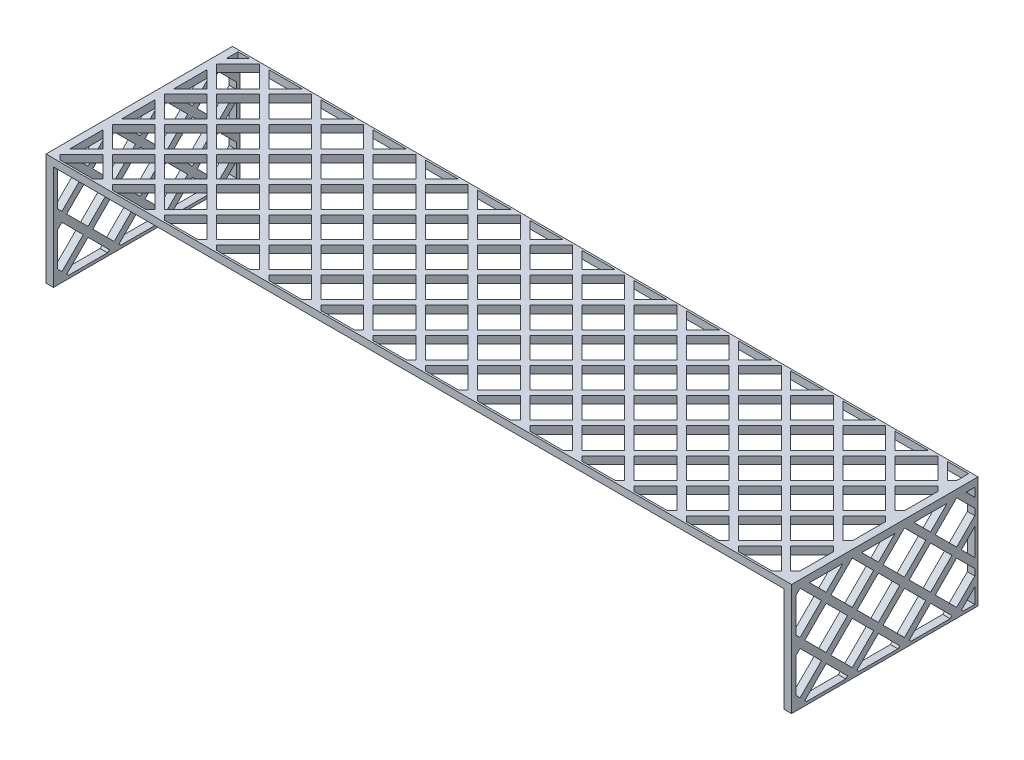
SolidWorks part; units mm, degrees
ref_plane "Front Plane" through (0, 0, 0) normal (0, 0, 1) x (1, 0, 0)
ref_plane "Top Plane" through (0, 0, 0) normal (0, 1, 0) x (1, 0, 0)
ref_plane "Right Plane" through (0, 0, 0) normal (1, 0, 0) x (0, 0, -1)
sketch "Sketch1" plane through (0, 0, 0) normal (0, 1, 0) x (1, 0, 0)
  line L1 (-70.9881, 12.5) -> (29.0119, 12.5)
  line L2 (-70.9881, 12.5) -> (-70.9881, -12.5)
  line L3 (-70.9881, -12.5) -> (29.0119, -12.5)
  line L4 (29.0119, 12.5) -> (29.0119, -12.5)
  point P0 (0, 0)
  dimension "D1" = 25
  dimension "D2" = 100
extrude "Boss-Extrude1" add sketch "Sketch1" along normal blind 1
sketch "Sketch2" plane through (0, 0, 0) normal (0, -1, 0) x (1, 0, 0)
  line L0 (-70.9881, 12.5) -> (29.0119, 12.5) construction
  line L1 (29.0119, -12.5) -> (28.0119, -12.5)
  line L2 (29.0119, -12.5) -> (29.0119, 12.5)
  line L3 (29.0119, 12.5) -> (28.0119, 12.5)
  line L4 (28.0119, -12.5) -> (28.0119, 12.5)
  line L6 (-70.9881, -12.5) -> (-69.9881, -12.5)
  line L7 (-70.9881, -12.5) -> (-70.9881, 12.5)
  line L8 (-70.9881, 12.5) -> (-69.9881, 12.5)
  line L9 (-69.9881, -12.5) -> (-69.9881, 12.5)
extrude "Boss-Extrude2" add sketch "Sketch2" along normal blind 14
sketch "Sketch4" plane through (0, 1, 0) normal (0, 1, 0) x (1, 0, 0)
  line L0 (-67.124, 12.25) -> (-69.9881, 9.3859)
  line L1 (-69.9881, 9.3859) -> (-67.124, 6.5219)
  line L2 (-67.124, 6.5219) -> (-64.2599, 9.3859)
  line L3 (-65.8521, 12.25) -> (-61.3959, 12.25)
  line L5 (-69.3521, -12.25) -> (-64.8959, -12.25)
  line L7 (-64.2599, 9.3859) -> (-67.124, 12.25)
  line L12 (-57.2599, 9.3859) -> (-60.124, 12.25)
  line L13 (-60.124, 12.25) -> (-62.9881, 9.3859)
  line L14 (-62.9881, 9.3859) -> (-60.124, 6.5219)
  line L15 (-60.124, 6.5219) -> (-57.2599, 9.3859)
  line L20 (-60.7599, 5.8859) -> (-63.624, 8.75)
  line L21 (-63.624, 8.75) -> (-66.4881, 5.8859)
  line L22 (-66.4881, 5.8859) -> (-63.624, 3.0219)
  line L23 (-63.624, 3.0219) -> (-60.7599, 5.8859)
  line L24 (-67.7599, 5.8859) -> (-69.9881, 8.1141)
  line L27 (-69.9881, 3.6578) -> (-67.7599, 5.8859)
  line L28 (-70.624, 8.75) -> (-73.4881, 5.8859) [skipped]
  line L29 (-73.4881, 5.8859) -> (-70.624, 3.0219) [skipped]
  line L32 (-65.8521, 12.25) -> (-63.624, 10.0219)
  line L33 (-63.624, 10.0219) -> (-61.3959, 12.25)
  line L34 (-60.7599, 12.8859) -> (-63.624, 15.75) [skipped]
  line L35 (-63.624, 15.75) -> (-66.4881, 12.8859) [skipped]
  line L36 (-64.2599, 2.3859) -> (-67.124, 5.25)
  line L37 (-67.124, 5.25) -> (-69.9881, 2.3859)
  line L38 (-69.9881, 2.3859) -> (-67.124, -0.4781)
  line L39 (-67.124, -0.4781) -> (-64.2599, 2.3859)
  line L40 (-64.2599, -4.6141) -> (-67.124, -1.75)
  line L41 (-67.124, -1.75) -> (-69.9881, -4.6141)
  line L42 (-69.9881, -4.6141) -> (-67.124, -7.4781)
  line L43 (-67.124, -7.4781) -> (-64.2599, -4.6141)
  line L44 (-64.2599, -11.6141) -> (-67.124, -8.75)
  line L45 (-67.124, -8.75) -> (-69.9881, -11.6141)
  line L46 (-69.9881, -11.6141) -> (-69.3521, -12.25)
  line L47 (-64.8959, -12.25) -> (-64.2599, -11.6141)
  line L48 (-69.9881, 8.1141) -> (-69.9881, 3.6578)
  line L50 (-67.7599, -1.1141) -> (-69.9881, 1.1141)
  line L51 (-69.9881, 1.1141) -> (-69.9881, -3.3422)
  line L52 (-69.9881, -3.3422) -> (-67.7599, -1.1141)
  line L53 (-67.7599, -8.1141) -> (-69.9881, -5.8859)
  line L54 (-69.9881, -5.8859) -> (-69.9881, -10.3422)
  line L55 (-69.9881, -10.3422) -> (-67.7599, -8.1141)
  line L56 (-69.9881, 12.25) -> (-69.9881, 10.6578)
  line L57 (-69.9881, 10.6578) -> (-68.3959, 12.25)
  line L58 (-68.3959, 12.25) -> (-69.9881, 12.25)
  line L59 (-57.2599, 9.3859) -> (-60.124, 12.25)
  line L60 (-67.7599, 12.8859) -> (-69.9881, 15.1141) [skipped]
  line L61 (-60.124, 12.25) -> (-62.9881, 9.3859)
  line L62 (-62.9881, 9.3859) -> (-60.124, 6.5219)
  line L63 (-60.124, 6.5219) -> (-57.2599, 9.3859)
  line L64 (-57.2599, 2.3859) -> (-60.124, 5.25)
  line L65 (-60.124, 5.25) -> (-62.9881, 2.3859)
  line L66 (-62.9881, 2.3859) -> (-60.124, -0.4781)
  line L67 (-60.124, -0.4781) -> (-57.2599, 2.3859)
  line L68 (-57.2599, -4.6141) -> (-60.124, -1.75)
  line L69 (-60.124, -1.75) -> (-62.9881, -4.6141)
  line L70 (-62.9881, -4.6141) -> (-60.124, -7.4781)
  line L71 (-60.124, -7.4781) -> (-57.2599, -4.6141)
  line L72 (-62.3521, -12.25) -> (-57.8959, -12.25)
  line L73 (-57.8959, -12.25) -> (-57.2599, -11.6141)
  line L74 (-57.2599, -11.6141) -> (-60.124, -8.75)
  line L75 (-60.124, -8.75) -> (-62.9881, -11.6141)
  line L76 (-62.9881, -11.6141) -> (-62.3521, -12.25)
  line L77 (-50.2599, 9.3859) -> (-53.124, 12.25)
  line L78 (-53.124, 12.25) -> (-55.9881, 9.3859)
  line L79 (-55.9881, 9.3859) -> (-53.124, 6.5219)
  line L80 (-53.124, 6.5219) -> (-50.2599, 9.3859)
  line L81 (-50.2599, 2.3859) -> (-53.124, 5.25)
  line L82 (-53.124, 5.25) -> (-55.9881, 2.3859)
  line L83 (-55.9881, 2.3859) -> (-53.124, -0.4781)
  line L84 (-53.124, -0.4781) -> (-50.2599, 2.3859)
  line L85 (-50.2599, -4.6141) -> (-53.124, -1.75)
  line L86 (-53.124, -1.75) -> (-55.9881, -4.6141)
  line L87 (-55.9881, -4.6141) -> (-53.124, -7.4781)
  line L88 (-53.124, -7.4781) -> (-50.2599, -4.6141)
  line L89 (-55.3521, -12.25) -> (-50.8959, -12.25)
  line L90 (-50.8959, -12.25) -> (-50.2599, -11.6141)
  line L91 (-50.2599, -11.6141) -> (-53.124, -8.75)
  line L92 (-53.124, -8.75) -> (-55.9881, -11.6141)
  line L93 (-55.9881, -11.6141) -> (-55.3521, -12.25)
  line L94 (-43.2599, 9.3859) -> (-46.124, 12.25)
  line L95 (-46.124, 12.25) -> (-48.9881, 9.3859)
  line L96 (-48.9881, 9.3859) -> (-46.124, 6.5219)
  line L97 (-46.124, 6.5219) -> (-43.2599, 9.3859)
  line L98 (-43.2599, 2.3859) -> (-46.124, 5.25)
  line L99 (-46.124, 5.25) -> (-48.9881, 2.3859)
  line L100 (-48.9881, 2.3859) -> (-46.124, -0.4781)
  line L101 (-46.124, -0.4781) -> (-43.2599, 2.3859)
  line L102 (-43.2599, -4.6141) -> (-46.124, -1.75)
  line L103 (-46.124, -1.75) -> (-48.9881, -4.6141)
  line L104 (-48.9881, -4.6141) -> (-46.124, -7.4781)
  line L105 (-46.124, -7.4781) -> (-43.2599, -4.6141)
  line L106 (-48.3521, -12.25) -> (-43.8959, -12.25)
  line L107 (-43.8959, -12.25) -> (-43.2599, -11.6141)
  line L108 (-43.2599, -11.6141) -> (-46.124, -8.75)
  line L109 (-46.124, -8.75) -> (-48.9881, -11.6141)
  line L110 (-48.9881, -11.6141) -> (-48.3521, -12.25)
  line L111 (-36.2599, 9.3859) -> (-39.124, 12.25)
  line L112 (-39.124, 12.25) -> (-41.9881, 9.3859)
  line L113 (-41.9881, 9.3859) -> (-39.124, 6.5219)
  line L114 (-39.124, 6.5219) -> (-36.2599, 9.3859)
  line L115 (-36.2599, 2.3859) -> (-39.124, 5.25)
  line L116 (-39.124, 5.25) -> (-41.9881, 2.3859)
  line L117 (-41.9881, 2.3859) -> (-39.124, -0.4781)
  line L118 (-39.124, -0.4781) -> (-36.2599, 2.3859)
  line L119 (-36.2599, -4.6141) -> (-39.124, -1.75)
  line L120 (-39.124, -1.75) -> (-41.9881, -4.6141)
  line L121 (-41.9881, -4.6141) -> (-39.124, -7.4781)
  line L122 (-39.124, -7.4781) -> (-36.2599, -4.6141)
  line L123 (-41.3521, -12.25) -> (-36.8959, -12.25)
  line L124 (-36.8959, -12.25) -> (-36.2599, -11.6141)
  line L125 (-36.2599, -11.6141) -> (-39.124, -8.75)
  line L126 (-39.124, -8.75) -> (-41.9881, -11.6141)
  line L127 (-41.9881, -11.6141) -> (-41.3521, -12.25)
  line L128 (-29.2599, 9.3859) -> (-32.124, 12.25)
  line L129 (-32.124, 12.25) -> (-34.9881, 9.3859)
  line L130 (-34.9881, 9.3859) -> (-32.124, 6.5219)
  line L131 (-32.124, 6.5219) -> (-29.2599, 9.3859)
  line L132 (-29.2599, 2.3859) -> (-32.124, 5.25)
  line L133 (-32.124, 5.25) -> (-34.9881, 2.3859)
  line L134 (-34.9881, 2.3859) -> (-32.124, -0.4781)
  line L135 (-32.124, -0.4781) -> (-29.2599, 2.3859)
  line L136 (-29.2599, -4.6141) -> (-32.124, -1.75)
  line L137 (-32.124, -1.75) -> (-34.9881, -4.6141)
  line L138 (-34.9881, -4.6141) -> (-32.124, -7.4781)
  line L139 (-32.124, -7.4781) -> (-29.2599, -4.6141)
  line L140 (-34.3521, -12.25) -> (-29.8959, -12.25)
  line L141 (-29.8959, -12.25) -> (-29.2599, -11.6141)
  line L142 (-29.2599, -11.6141) -> (-32.124, -8.75)
  line L143 (-32.124, -8.75) -> (-34.9881, -11.6141)
  line L144 (-34.9881, -11.6141) -> (-34.3521, -12.25)
  line L145 (-22.2599, 9.3859) -> (-25.124, 12.25)
  line L146 (-25.124, 12.25) -> (-27.9881, 9.3859)
  line L147 (-27.9881, 9.3859) -> (-25.124, 6.5219)
  line L148 (-25.124, 6.5219) -> (-22.2599, 9.3859)
  line L149 (-22.2599, 2.3859) -> (-25.124, 5.25)
  line L150 (-25.124, 5.25) -> (-27.9881, 2.3859)
  line L151 (-27.9881, 2.3859) -> (-25.124, -0.4781)
  line L152 (-25.124, -0.4781) -> (-22.2599, 2.3859)
  line L153 (-22.2599, -4.6141) -> (-25.124, -1.75)
  line L154 (-25.124, -1.75) -> (-27.9881, -4.6141)
  line L155 (-27.9881, -4.6141) -> (-25.124, -7.4781)
  line L156 (-25.124, -7.4781) -> (-22.2599, -4.6141)
  line L157 (-27.3521, -12.25) -> (-22.8959, -12.25)
  line L158 (-22.8959, -12.25) -> (-22.2599, -11.6141)
  line L159 (-22.2599, -11.6141) -> (-25.124, -8.75)
  line L160 (-25.124, -8.75) -> (-27.9881, -11.6141)
  line L161 (-27.9881, -11.6141) -> (-27.3521, -12.25)
  line L162 (-15.2599, 9.3859) -> (-18.124, 12.25)
  line L163 (-18.124, 12.25) -> (-20.9881, 9.3859)
  line L164 (-20.9881, 9.3859) -> (-18.124, 6.5219)
  line L165 (-18.124, 6.5219) -> (-15.2599, 9.3859)
  line L166 (-15.2599, 2.3859) -> (-18.124, 5.25)
  line L167 (-18.124, 5.25) -> (-20.9881, 2.3859)
  line L168 (-20.9881, 2.3859) -> (-18.124, -0.4781)
  line L169 (-18.124, -0.4781) -> (-15.2599, 2.3859)
  line L170 (-15.2599, -4.6141) -> (-18.124, -1.75)
  line L171 (-18.124, -1.75) -> (-20.9881, -4.6141)
  line L172 (-20.9881, -4.6141) -> (-18.124, -7.4781)
  line L173 (-18.124, -7.4781) -> (-15.2599, -4.6141)
  line L174 (-20.3521, -12.25) -> (-15.8959, -12.25)
  line L175 (-15.8959, -12.25) -> (-15.2599, -11.6141)
  line L176 (-15.2599, -11.6141) -> (-18.124, -8.75)
  line L177 (-18.124, -8.75) -> (-20.9881, -11.6141)
  line L178 (-20.9881, -11.6141) -> (-20.3521, -12.25)
  line L179 (-8.2599, 9.3859) -> (-11.124, 12.25)
  line L180 (-11.124, 12.25) -> (-13.9881, 9.3859)
  line L181 (-13.9881, 9.3859) -> (-11.124, 6.5219)
  line L182 (-11.124, 6.5219) -> (-8.2599, 9.3859)
  line L183 (-8.2599, 2.3859) -> (-11.124, 5.25)
  line L184 (-11.124, 5.25) -> (-13.9881, 2.3859)
  line L185 (-13.9881, 2.3859) -> (-11.124, -0.4781)
  line L186 (-11.124, -0.4781) -> (-8.2599, 2.3859)
  line L187 (-8.2599, -4.6141) -> (-11.124, -1.75)
  line L188 (-11.124, -1.75) -> (-13.9881, -4.6141)
  line L189 (-13.9881, -4.6141) -> (-11.124, -7.4781)
  line L190 (-11.124, -7.4781) -> (-8.2599, -4.6141)
  line L191 (-13.3521, -12.25) -> (-8.8959, -12.25)
  line L192 (-8.8959, -12.25) -> (-8.2599, -11.6141)
  line L193 (-8.2599, -11.6141) -> (-11.124, -8.75)
  line L194 (-11.124, -8.75) -> (-13.9881, -11.6141)
  line L195 (-13.9881, -11.6141) -> (-13.3521, -12.25)
  line L196 (-1.2599, 9.3859) -> (-4.124, 12.25)
  line L197 (-4.124, 12.25) -> (-6.9881, 9.3859)
  line L198 (-6.9881, 9.3859) -> (-4.124, 6.5219)
  line L199 (-4.124, 6.5219) -> (-1.2599, 9.3859)
  line L200 (-1.2599, 2.3859) -> (-4.124, 5.25)
  line L201 (-4.124, 5.25) -> (-6.9881, 2.3859)
  line L202 (-6.9881, 2.3859) -> (-4.124, -0.4781)
  line L203 (-4.124, -0.4781) -> (-1.2599, 2.3859)
  line L204 (-1.2599, -4.6141) -> (-4.124, -1.75)
  line L205 (-4.124, -1.75) -> (-6.9881, -4.6141)
  line L206 (-6.9881, -4.6141) -> (-4.124, -7.4781)
  line L207 (-4.124, -7.4781) -> (-1.2599, -4.6141)
  line L208 (-6.3521, -12.25) -> (-1.8959, -12.25)
  line L209 (-1.8959, -12.25) -> (-1.2599, -11.6141)
  line L210 (-1.2599, -11.6141) -> (-4.124, -8.75)
  line L211 (-4.124, -8.75) -> (-6.9881, -11.6141)
  line L212 (-6.9881, -11.6141) -> (-6.3521, -12.25)
  line L213 (5.7401, 9.3859) -> (2.876, 12.25)
  line L214 (2.876, 12.25) -> (0.0119, 9.3859)
  line L215 (0.0119, 9.3859) -> (2.876, 6.5219)
  line L216 (2.876, 6.5219) -> (5.7401, 9.3859)
  line L217 (5.7401, 2.3859) -> (2.876, 5.25)
  line L218 (2.876, 5.25) -> (0.0119, 2.3859)
  line L219 (0.0119, 2.3859) -> (2.876, -0.4781)
  line L220 (2.876, -0.4781) -> (5.7401, 2.3859)
  line L221 (5.7401, -4.6141) -> (2.876, -1.75)
  line L222 (2.876, -1.75) -> (0.0119, -4.6141)
  line L223 (0.0119, -4.6141) -> (2.876, -7.4781)
  line L224 (2.876, -7.4781) -> (5.7401, -4.6141)
  line L225 (0.6479, -12.25) -> (5.1041, -12.25)
  line L226 (5.1041, -12.25) -> (5.7401, -11.6141)
  line L227 (5.7401, -11.6141) -> (2.876, -8.75)
  line L228 (2.876, -8.75) -> (0.0119, -11.6141)
  line L229 (0.0119, -11.6141) -> (0.6479, -12.25)
  line L230 (12.7401, 9.3859) -> (9.876, 12.25)
  line L231 (9.876, 12.25) -> (7.0119, 9.3859)
  line L232 (7.0119, 9.3859) -> (9.876, 6.5219)
  line L233 (9.876, 6.5219) -> (12.7401, 9.3859)
  line L234 (12.7401, 2.3859) -> (9.876, 5.25)
  line L235 (9.876, 5.25) -> (7.0119, 2.3859)
  line L236 (7.0119, 2.3859) -> (9.876, -0.4781)
  line L237 (9.876, -0.4781) -> (12.7401, 2.3859)
  line L238 (12.7401, -4.6141) -> (9.876, -1.75)
  line L239 (9.876, -1.75) -> (7.0119, -4.6141)
  line L240 (7.0119, -4.6141) -> (9.876, -7.4781)
  line L241 (9.876, -7.4781) -> (12.7401, -4.6141)
  line L242 (7.6479, -12.25) -> (12.1041, -12.25)
  line L243 (12.1041, -12.25) -> (12.7401, -11.6141)
  line L244 (12.7401, -11.6141) -> (9.876, -8.75)
  line L245 (9.876, -8.75) -> (7.0119, -11.6141)
  line L246 (7.0119, -11.6141) -> (7.6479, -12.25)
  line L247 (19.7401, 9.3859) -> (16.876, 12.25)
  line L248 (16.876, 12.25) -> (14.0119, 9.3859)
  line L249 (14.0119, 9.3859) -> (16.876, 6.5219)
  line L250 (16.876, 6.5219) -> (19.7401, 9.3859)
  line L251 (19.7401, 2.3859) -> (16.876, 5.25)
  line L252 (16.876, 5.25) -> (14.0119, 2.3859)
  line L253 (14.0119, 2.3859) -> (16.876, -0.4781)
  line L254 (16.876, -0.4781) -> (19.7401, 2.3859)
  line L255 (19.7401, -4.6141) -> (16.876, -1.75)
  line L256 (16.876, -1.75) -> (14.0119, -4.6141)
  line L257 (14.0119, -4.6141) -> (16.876, -7.4781)
  line L258 (16.876, -7.4781) -> (19.7401, -4.6141)
  line L259 (14.6479, -12.25) -> (19.1041, -12.25)
  line L260 (19.1041, -12.25) -> (19.7401, -11.6141)
  line L261 (19.7401, -11.6141) -> (16.876, -8.75)
  line L262 (16.876, -8.75) -> (14.0119, -11.6141)
  line L263 (14.0119, -11.6141) -> (14.6479, -12.25)
  line L264 (26.7401, 9.3859) -> (23.876, 12.25)
  line L265 (23.876, 12.25) -> (21.0119, 9.3859)
  line L266 (21.0119, 9.3859) -> (23.876, 6.5219)
  line L267 (23.876, 6.5219) -> (26.7401, 9.3859)
  line L268 (26.7401, 2.3859) -> (23.876, 5.25)
  line L269 (23.876, 5.25) -> (21.0119, 2.3859)
  line L270 (21.0119, 2.3859) -> (23.876, -0.4781)
  line L271 (23.876, -0.4781) -> (26.7401, 2.3859)
  line L272 (26.7401, -4.6141) -> (23.876, -1.75)
  line L273 (23.876, -1.75) -> (21.0119, -4.6141)
  line L274 (21.0119, -4.6141) -> (23.876, -7.4781)
  line L275 (23.876, -7.4781) -> (26.7401, -4.6141)
  line L276 (21.6479, -12.25) -> (26.1041, -12.25)
  line L277 (26.1041, -12.25) -> (26.7401, -11.6141)
  line L278 (26.7401, -11.6141) -> (23.876, -8.75)
  line L279 (23.876, -8.75) -> (21.0119, -11.6141)
  line L280 (21.0119, -11.6141) -> (21.6479, -12.25)
  line L281 (-60.7599, -1.1141) -> (-63.624, 1.75)
  line L282 (-63.624, 1.75) -> (-66.4881, -1.1141)
  line L283 (-66.4881, -1.1141) -> (-63.624, -3.9781)
  line L284 (-63.624, -3.9781) -> (-60.7599, -1.1141)
  line L285 (-60.7599, -8.1141) -> (-63.624, -5.25)
  line L286 (-63.624, -5.25) -> (-66.4881, -8.1141)
  line L287 (-66.4881, -8.1141) -> (-63.624, -10.9781)
  line L288 (-63.624, -10.9781) -> (-60.7599, -8.1141)
  line L289 (-58.8521, 12.25) -> (-54.3959, 12.25)
  line L290 (-56.624, 10.0219) -> (-54.3959, 12.25)
  line L291 (-58.8521, 12.25) -> (-56.624, 10.0219)
  line L292 (-53.7599, 5.8859) -> (-56.624, 8.75)
  line L293 (-56.624, 8.75) -> (-59.4881, 5.8859)
  line L294 (-59.4881, 5.8859) -> (-56.624, 3.0219)
  line L295 (-56.624, 3.0219) -> (-53.7599, 5.8859)
  line L296 (-53.7599, -1.1141) -> (-56.624, 1.75)
  line L297 (-56.624, 1.75) -> (-59.4881, -1.1141)
  line L298 (-59.4881, -1.1141) -> (-56.624, -3.9781)
  line L299 (-56.624, -3.9781) -> (-53.7599, -1.1141)
  line L300 (-53.7599, -8.1141) -> (-56.624, -5.25)
  line L301 (-56.624, -5.25) -> (-59.4881, -8.1141)
  line L302 (-59.4881, -8.1141) -> (-56.624, -10.9781)
  line L303 (-56.624, -10.9781) -> (-53.7599, -8.1141)
  line L304 (-51.8521, 12.25) -> (-47.3959, 12.25)
  line L305 (-49.624, 10.0219) -> (-47.3959, 12.25)
  line L306 (-51.8521, 12.25) -> (-49.624, 10.0219)
  line L307 (-46.7599, 5.8859) -> (-49.624, 8.75)
  line L308 (-49.624, 8.75) -> (-52.4881, 5.8859)
  line L309 (-52.4881, 5.8859) -> (-49.624, 3.0219)
  line L310 (-49.624, 3.0219) -> (-46.7599, 5.8859)
  line L311 (-46.7599, -1.1141) -> (-49.624, 1.75)
  line L312 (-49.624, 1.75) -> (-52.4881, -1.1141)
  line L313 (-52.4881, -1.1141) -> (-49.624, -3.9781)
  line L314 (-49.624, -3.9781) -> (-46.7599, -1.1141)
  line L315 (-46.7599, -8.1141) -> (-49.624, -5.25)
  line L316 (-49.624, -5.25) -> (-52.4881, -8.1141)
  line L317 (-52.4881, -8.1141) -> (-49.624, -10.9781)
  line L318 (-49.624, -10.9781) -> (-46.7599, -8.1141)
  line L319 (-44.8521, 12.25) -> (-40.3959, 12.25)
  line L320 (-42.624, 10.0219) -> (-40.3959, 12.25)
  line L321 (-44.8521, 12.25) -> (-42.624, 10.0219)
  line L322 (-39.7599, 5.8859) -> (-42.624, 8.75)
  line L323 (-42.624, 8.75) -> (-45.4881, 5.8859)
  line L324 (-45.4881, 5.8859) -> (-42.624, 3.0219)
  line L325 (-42.624, 3.0219) -> (-39.7599, 5.8859)
  line L326 (-39.7599, -1.1141) -> (-42.624, 1.75)
  line L327 (-42.624, 1.75) -> (-45.4881, -1.1141)
  line L328 (-45.4881, -1.1141) -> (-42.624, -3.9781)
  line L329 (-42.624, -3.9781) -> (-39.7599, -1.1141)
  line L330 (-39.7599, -8.1141) -> (-42.624, -5.25)
  line L331 (-42.624, -5.25) -> (-45.4881, -8.1141)
  line L332 (-45.4881, -8.1141) -> (-42.624, -10.9781)
  line L333 (-42.624, -10.9781) -> (-39.7599, -8.1141)
  line L334 (-37.8521, 12.25) -> (-33.3959, 12.25)
  line L335 (-35.624, 10.0219) -> (-33.3959, 12.25)
  line L336 (-37.8521, 12.25) -> (-35.624, 10.0219)
  line L337 (-32.7599, 5.8859) -> (-35.624, 8.75)
  line L338 (-35.624, 8.75) -> (-38.4881, 5.8859)
  line L339 (-38.4881, 5.8859) -> (-35.624, 3.0219)
  line L340 (-35.624, 3.0219) -> (-32.7599, 5.8859)
  line L341 (-32.7599, -1.1141) -> (-35.624, 1.75)
  line L342 (-35.624, 1.75) -> (-38.4881, -1.1141)
  line L343 (-38.4881, -1.1141) -> (-35.624, -3.9781)
  line L344 (-35.624, -3.9781) -> (-32.7599, -1.1141)
  line L345 (-32.7599, -8.1141) -> (-35.624, -5.25)
  line L346 (-35.624, -5.25) -> (-38.4881, -8.1141)
  line L347 (-38.4881, -8.1141) -> (-35.624, -10.9781)
  line L348 (-35.624, -10.9781) -> (-32.7599, -8.1141)
  line L349 (-30.8521, 12.25) -> (-26.3959, 12.25)
  line L350 (-28.624, 10.0219) -> (-26.3959, 12.25)
  line L351 (-30.8521, 12.25) -> (-28.624, 10.0219)
  line L352 (-25.7599, 5.8859) -> (-28.624, 8.75)
  line L353 (-28.624, 8.75) -> (-31.4881, 5.8859)
  line L354 (-31.4881, 5.8859) -> (-28.624, 3.0219)
  line L355 (-28.624, 3.0219) -> (-25.7599, 5.8859)
  line L356 (-25.7599, -1.1141) -> (-28.624, 1.75)
  line L357 (-28.624, 1.75) -> (-31.4881, -1.1141)
  line L358 (-31.4881, -1.1141) -> (-28.624, -3.9781)
  line L359 (-28.624, -3.9781) -> (-25.7599, -1.1141)
  line L360 (-25.7599, -8.1141) -> (-28.624, -5.25)
  line L361 (-28.624, -5.25) -> (-31.4881, -8.1141)
  line L362 (-31.4881, -8.1141) -> (-28.624, -10.9781)
  line L363 (-28.624, -10.9781) -> (-25.7599, -8.1141)
  line L364 (-23.8521, 12.25) -> (-19.3959, 12.25)
  line L365 (-21.624, 10.0219) -> (-19.3959, 12.25)
  line L366 (-23.8521, 12.25) -> (-21.624, 10.0219)
  line L367 (-18.7599, 5.8859) -> (-21.624, 8.75)
  line L368 (-21.624, 8.75) -> (-24.4881, 5.8859)
  line L369 (-24.4881, 5.8859) -> (-21.624, 3.0219)
  line L370 (-21.624, 3.0219) -> (-18.7599, 5.8859)
  line L371 (-18.7599, -1.1141) -> (-21.624, 1.75)
  line L372 (-21.624, 1.75) -> (-24.4881, -1.1141)
  line L373 (-24.4881, -1.1141) -> (-21.624, -3.9781)
  line L374 (-21.624, -3.9781) -> (-18.7599, -1.1141)
  line L375 (-18.7599, -8.1141) -> (-21.624, -5.25)
  line L376 (-21.624, -5.25) -> (-24.4881, -8.1141)
  line L377 (-24.4881, -8.1141) -> (-21.624, -10.9781)
  line L378 (-21.624, -10.9781) -> (-18.7599, -8.1141)
  line L379 (-16.8521, 12.25) -> (-12.3959, 12.25)
  line L380 (-14.624, 10.0219) -> (-12.3959, 12.25)
  line L381 (-16.8521, 12.25) -> (-14.624, 10.0219)
  line L382 (-11.7599, 5.8859) -> (-14.624, 8.75)
  line L383 (-14.624, 8.75) -> (-17.4881, 5.8859)
  line L384 (-17.4881, 5.8859) -> (-14.624, 3.0219)
  line L385 (-14.624, 3.0219) -> (-11.7599, 5.8859)
  line L386 (-11.7599, -1.1141) -> (-14.624, 1.75)
  line L387 (-14.624, 1.75) -> (-17.4881, -1.1141)
  line L388 (-17.4881, -1.1141) -> (-14.624, -3.9781)
  line L389 (-14.624, -3.9781) -> (-11.7599, -1.1141)
  line L390 (-11.7599, -8.1141) -> (-14.624, -5.25)
  line L391 (-14.624, -5.25) -> (-17.4881, -8.1141)
  line L392 (-17.4881, -8.1141) -> (-14.624, -10.9781)
  line L393 (-14.624, -10.9781) -> (-11.7599, -8.1141)
  line L394 (-9.8521, 12.25) -> (-5.3959, 12.25)
  line L395 (-7.624, 10.0219) -> (-5.3959, 12.25)
  line L396 (-9.8521, 12.25) -> (-7.624, 10.0219)
  line L397 (-4.7599, 5.8859) -> (-7.624, 8.75)
  line L398 (-7.624, 8.75) -> (-10.4881, 5.8859)
  line L399 (-10.4881, 5.8859) -> (-7.624, 3.0219)
  line L400 (-7.624, 3.0219) -> (-4.7599, 5.8859)
  line L401 (-4.7599, -1.1141) -> (-7.624, 1.75)
  line L402 (-7.624, 1.75) -> (-10.4881, -1.1141)
  line L403 (-10.4881, -1.1141) -> (-7.624, -3.9781)
  line L404 (-7.624, -3.9781) -> (-4.7599, -1.1141)
  line L405 (-4.7599, -8.1141) -> (-7.624, -5.25)
  line L406 (-7.624, -5.25) -> (-10.4881, -8.1141)
  line L407 (-10.4881, -8.1141) -> (-7.624, -10.9781)
  line L408 (-7.624, -10.9781) -> (-4.7599, -8.1141)
  line L409 (-2.8521, 12.25) -> (1.6041, 12.25)
  line L410 (-0.624, 10.0219) -> (1.6041, 12.25)
  line L411 (-2.8521, 12.25) -> (-0.624, 10.0219)
  line L412 (2.2401, 5.8859) -> (-0.624, 8.75)
  line L413 (-0.624, 8.75) -> (-3.4881, 5.8859)
  line L414 (-3.4881, 5.8859) -> (-0.624, 3.0219)
  line L415 (-0.624, 3.0219) -> (2.2401, 5.8859)
  line L416 (2.2401, -1.1141) -> (-0.624, 1.75)
  line L417 (-0.624, 1.75) -> (-3.4881, -1.1141)
  line L418 (-3.4881, -1.1141) -> (-0.624, -3.9781)
  line L419 (-0.624, -3.9781) -> (2.2401, -1.1141)
  line L420 (2.2401, -8.1141) -> (-0.624, -5.25)
  line L421 (-0.624, -5.25) -> (-3.4881, -8.1141)
  line L422 (-3.4881, -8.1141) -> (-0.624, -10.9781)
  line L423 (-0.624, -10.9781) -> (2.2401, -8.1141)
  line L424 (4.1479, 12.25) -> (8.6041, 12.25)
  line L425 (6.376, 10.0219) -> (8.6041, 12.25)
  line L426 (4.1479, 12.25) -> (6.376, 10.0219)
  line L427 (9.2401, 5.8859) -> (6.376, 8.75)
  line L428 (6.376, 8.75) -> (3.5119, 5.8859)
  line L429 (3.5119, 5.8859) -> (6.376, 3.0219)
  line L430 (6.376, 3.0219) -> (9.2401, 5.8859)
  line L431 (9.2401, -1.1141) -> (6.376, 1.75)
  line L432 (6.376, 1.75) -> (3.5119, -1.1141)
  line L433 (3.5119, -1.1141) -> (6.376, -3.9781)
  line L434 (6.376, -3.9781) -> (9.2401, -1.1141)
  line L435 (9.2401, -8.1141) -> (6.376, -5.25)
  line L436 (6.376, -5.25) -> (3.5119, -8.1141)
  line L437 (3.5119, -8.1141) -> (6.376, -10.9781)
  line L438 (6.376, -10.9781) -> (9.2401, -8.1141)
  line L439 (11.1479, 12.25) -> (15.6041, 12.25)
  line L440 (13.376, 10.0219) -> (15.6041, 12.25)
  line L441 (11.1479, 12.25) -> (13.376, 10.0219)
  line L442 (16.2401, 5.8859) -> (13.376, 8.75)
  line L443 (13.376, 8.75) -> (10.5119, 5.8859)
  line L444 (10.5119, 5.8859) -> (13.376, 3.0219)
  line L445 (13.376, 3.0219) -> (16.2401, 5.8859)
  line L446 (16.2401, -1.1141) -> (13.376, 1.75)
  line L447 (13.376, 1.75) -> (10.5119, -1.1141)
  line L448 (10.5119, -1.1141) -> (13.376, -3.9781)
  line L449 (13.376, -3.9781) -> (16.2401, -1.1141)
  line L450 (16.2401, -8.1141) -> (13.376, -5.25)
  line L451 (13.376, -5.25) -> (10.5119, -8.1141)
  line L452 (10.5119, -8.1141) -> (13.376, -10.9781)
  line L453 (13.376, -10.9781) -> (16.2401, -8.1141)
  line L454 (18.1479, 12.25) -> (22.6041, 12.25)
  line L455 (20.376, 10.0219) -> (22.6041, 12.25)
  line L456 (18.1479, 12.25) -> (20.376, 10.0219)
  line L457 (23.2401, 5.8859) -> (20.376, 8.75)
  line L458 (20.376, 8.75) -> (17.5119, 5.8859)
  line L459 (17.5119, 5.8859) -> (20.376, 3.0219)
  line L460 (20.376, 3.0219) -> (23.2401, 5.8859)
  line L461 (23.2401, -1.1141) -> (20.376, 1.75)
  line L462 (20.376, 1.75) -> (17.5119, -1.1141)
  line L463 (17.5119, -1.1141) -> (20.376, -3.9781)
  line L464 (20.376, -3.9781) -> (23.2401, -1.1141)
  line L465 (23.2401, -8.1141) -> (20.376, -5.25)
  line L466 (20.376, -5.25) -> (17.5119, -8.1141)
  line L467 (17.5119, -8.1141) -> (20.376, -10.9781)
  line L468 (20.376, -10.9781) -> (23.2401, -8.1141)
  line L469 (25.1479, 12.25) -> (28.0119, 12.25)
  line L470 (27.376, 10.0219) -> (28.0119, 10.6578)
  line L471 (25.1479, 12.25) -> (27.376, 10.0219)
  line L472 (28.0119, 8.1141) -> (27.376, 8.75)
  line L473 (27.376, 8.75) -> (24.5119, 5.8859)
  line L474 (24.5119, 5.8859) -> (27.376, 3.0219)
  line L475 (27.376, 3.0219) -> (28.0119, 3.6578)
  line L476 (28.0119, 1.1141) -> (27.376, 1.75)
  line L477 (27.376, 1.75) -> (24.5119, -1.1141)
  line L478 (24.5119, -1.1141) -> (27.376, -3.9781)
  line L479 (27.376, -3.9781) -> (28.0119, -3.3422)
  line L480 (28.0119, -5.8859) -> (27.376, -5.25)
  line L481 (27.376, -5.25) -> (24.5119, -8.1141)
  line L482 (24.5119, -8.1141) -> (27.376, -10.9781)
  line L483 (27.376, -10.9781) -> (28.0119, -10.3422)
  line L484 (28.0119, 12.25) -> (28.0119, 10.6578)
  line L486 (28.0119, 8.1141) -> (28.0119, 3.6578)
  line L487 (28.0119, 1.1141) -> (28.0119, -3.3422)
  line L488 (28.0119, -5.8859) -> (28.0119, -10.3422)
  point P8 (-20.9881, 0)
  dimension "D1" = 2
  dimension "D2" = 2
  dimension "D3" = 2
  dimension "D4" = 4
  dimension "D5" = 3
  dimension "D6" = 2
  dimension "D7" = 14
  dimension "D8" = 3
  dimension "D9" = 14
extrude "Cut-Extrude4" cut sketch "Sketch4" against normal blind 2
sketch "Sketch5" plane through (-70.9881, 0, 0) normal (-1, 0, 0) x (0, 0, 1)
  line L1 (-12.0677, -2.4319) -> (-9.6364, 0)
  line L3 (-12.0677, -3.2966) -> (-9.6364, -5.7279)
  line L4 (-9.6364, -5.7279) -> (-6.7728, -2.8643)
  line L5 (-6.7728, -2.8643) -> (-9.6364, 0)
  line L6 (0.2272, -2.8643) -> (-2.6364, 0)
  line L7 (-5.5, -2.8643) -> (-2.6364, 0)
  line L8 (-5.5, -2.8643) -> (-2.6364, -5.7279)
  line L9 (-2.6364, -5.7279) -> (0.2272, -2.8643)
  line L10 (7.2272, -2.8643) -> (4.3636, 0)
  line L11 (1.5, -2.8643) -> (4.3636, 0)
  line L12 (1.5, -2.8643) -> (4.3636, -5.7279)
  line L13 (4.3636, -5.7279) -> (7.2272, -2.8643)
  line L14 (11.932, -0.5685) -> (11.3636, 0)
  line L15 (8.5, -2.8643) -> (11.3636, 0)
  line L16 (8.5, -2.8643) -> (11.3636, -5.7279)
  line L17 (11.3636, -5.7279) -> (11.932, -5.1595)
  line L22 (-3.2728, -6.3643) -> (-6.1364, -3.5)
  line L23 (-9, -6.3643) -> (-6.1364, -3.5)
  line L24 (-9, -6.3643) -> (-6.1364, -9.2279)
  line L25 (-6.1364, -9.2279) -> (-3.2728, -6.3643)
  line L28 (-8.3643, 0) -> (-6.1364, -2.2279)
  line L29 (-6.1364, -2.2279) -> (-3.9085, 0)
  line L30 (-9, 0.6357) -> (-6.1364, 3.5) [skipped]
  line L31 (-3.2728, 0.6357) -> (-6.1364, 3.5) [skipped]
  line L32 (-8.3643, 0) -> (-3.9085, 0)
  line L33 (-1.3643, 0) -> (3.0915, 0)
  line L35 (-12.0677, -1.1592) -> (-10.9085, 0)
  line L37 (-1.3643, 0) -> (0.8636, -2.2279)
  line L38 (0.8636, -2.2279) -> (3.0915, 0)
  line L39 (-1.3643, 0) -> (3.0915, 0)
  line L40 (5.6357, 0) -> (7.8636, -2.2279)
  line L41 (7.8636, -2.2279) -> (10.0915, 0)
  line L42 (5.6357, 0) -> (10.0915, 0)
  line L43 (5.6357, 0) -> (10.0915, 0)
  line L44 (-12.0677, 0) -> (-10.9085, 0)
  line L45 (-10.2728, -6.3643) -> (-12.0677, -4.5689)
  line L46 (-15.3643, 0) -> (-13.1364, -2.2279) [skipped]
  line L49 (-12.0677, -8.1592) -> (-10.2728, -6.3643)
  line L50 (3.7272, -6.3643) -> (0.8636, -3.5)
  line L51 (-2, -6.3643) -> (0.8636, -3.5)
  line L52 (-2, -6.3643) -> (0.8636, -9.2279)
  line L53 (0.8636, -9.2279) -> (3.7272, -6.3643)
  line L54 (10.7272, -6.3643) -> (7.8636, -3.5)
  line L55 (5, -6.3643) -> (7.8636, -3.5)
  line L56 (5, -6.3643) -> (7.8636, -9.2279)
  line L57 (7.8636, -9.2279) -> (10.7272, -6.3643)
  line L58 (-6.7728, -9.8643) -> (-9.6364, -7)
  line L59 (-12.0677, -9.4319) -> (-9.6364, -7)
  line L60 (-12.0677, -10.2966) -> (-9.6364, -12.7279)
  line L61 (-9.6364, -12.7279) -> (-6.7728, -9.8643)
  line L62 (0.2272, -9.8643) -> (-2.6364, -7)
  line L63 (-5.5, -9.8643) -> (-2.6364, -7)
  line L64 (-5.5, -9.8643) -> (-2.6364, -12.7279)
  line L65 (-2.6364, -12.7279) -> (0.2272, -9.8643)
  line L66 (7.2272, -9.8643) -> (4.3636, -7)
  line L67 (1.5, -9.8643) -> (4.3636, -7)
  line L68 (1.5, -9.8643) -> (4.3636, -12.7279)
  line L69 (4.3636, -12.7279) -> (7.2272, -9.8643)
  line L70 (11.932, -7.5685) -> (11.3636, -7)
  line L71 (8.5, -9.8643) -> (11.3636, -7)
  line L72 (8.5, -9.8643) -> (11.3636, -12.7279)
  line L73 (11.3636, -12.7279) -> (11.932, -12.1595)
  line L74 (-10.2728, -13.3643) -> (-12.0677, -11.5689)
  line L77 (-10.5125, -13.6041) -> (-10.2728, -13.3643)
  line L78 (-3.2728, -13.3643) -> (-6.1364, -10.5)
  line L79 (-9, -13.3643) -> (-6.1364, -10.5)
  line L80 (-9, -13.3643) -> (-8.7602, -13.6041)
  line L81 (-3.5125, -13.6041) -> (-3.2728, -13.3643)
  line L82 (3.7272, -13.3643) -> (0.8636, -10.5)
  line L83 (-2, -13.3643) -> (0.8636, -10.5)
  line L84 (-2, -13.3643) -> (-1.7602, -13.6041)
  line L85 (3.4875, -13.6041) -> (3.7272, -13.3643)
  line L86 (10.7272, -13.3643) -> (7.8636, -10.5)
  line L87 (5, -13.3643) -> (7.8636, -10.5)
  line L88 (5, -13.3643) -> (5.2398, -13.6041)
  line L89 (10.4875, -13.6041) -> (10.7272, -13.3643)
  line L90 (-12.5, 0) -> (-10.9085, 0) [skipped]
  line L91 (-12.0677, -13.6041) -> (-12.0677, -11.5689)
  line L99 (11.932, -0.5685) -> (11.932, -5.1595)
  line L101 (-16, -6.3643) -> (-13.1364, -9.2279) [skipped]
  line L102 (-16, -6.3643) -> (-13.1364, -3.5) [skipped]
  line L105 (-12.0677, -10.2966) -> (-12.0677, -9.4319)
  line L106 (-12.0677, -13.6041) -> (-10.5125, -13.6041)
  line L107 (-8.7602, -13.6041) -> (-3.5125, -13.6041)
  line L108 (-1.7602, -13.6041) -> (3.4875, -13.6041)
  line L109 (5.2398, -13.6041) -> (10.4875, -13.6041)
  line L110 (11.932, -7.5685) -> (11.932, -12.1595)
  line L111 (-12.0677, -1.1592) -> (-12.0677, 0)
  line L112 (-12.0677, -3.2966) -> (-12.0677, -2.4319)
  line L113 (-12.0677, -8.1592) -> (-12.0677, -4.5689)
  dimension "D1" = 4
  dimension "D2" = 2
  dimension "D3" = 2
  dimension "D4" = 3
  dimension "D5" = 2
  dimension "D6" = 3
  dimension "D7" = 2
  dimension "D8" = 2
extrude "Cut-Extrude11" cut sketch "Sketch5" against normal blind 129 contours L111 L35 L44 | L112 L3 L4 L5 L1 | L32 L28 L29 | L8 L9 L6 L7 | L37 L38 L33 | L12 L13 L10 L11 | L42 L40 L41 | L99 L14 L15 L16 L17 | L56 L57 L54 L55 | L110 L70 L71 L72 L73 | L88 L109 L89 L86 L87 | L68 L69 L66 L67 | L52 L53 L50 L51 | L64 L65 L62 L63 | L24 L25 L22 L23 | L105 L60 L61 L58 L59 | L91 L106 L77 L74 | L80 L107 L81 L78 L79 | L84 L108 L85 L82 L83 | L113 L45 L49 region at (-70.9881, -2.864, -9.6067) region at (-70.9881, -2.864, -2.6364) region at (-70.9881, -2.864, 4.3636) region at (-70.9881, -2.864, 10.7326) region at (-70.9881, -6.364, -6.1364) region at (-70.9881, -0.7426, -6.1364) region at (-70.9881, -0.7426, 0.8636) region at (-70.9881, -0.3864, -11.6813) region at (-70.9881, -0.7426, 7.8636) region at (-70.9881, -6.364, 0.8636) region at (-70.9881, -6.364, 7.8636) region at (-70.9881, -9.864, -9.6067) region at (-70.9881, -9.864, -2.6364) region at (-70.9881, -9.864, 4.3636) region at (-70.9881, -9.864, 10.7326) region at (-70.9881, -12.9086, -11.4214) region at (-70.9881, -12.5578, -6.1364) region at (-70.9881, -12.5578, 0.8636) region at (-70.9881, -12.5578, 7.8636)
